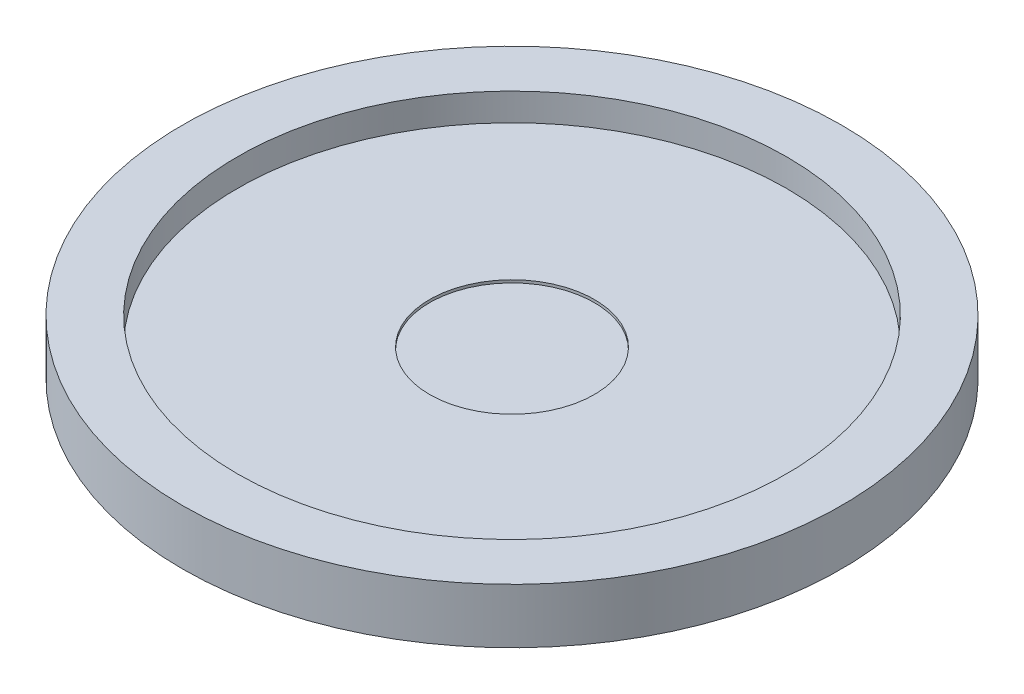
SolidWorks part; units mm, degrees
ref_plane "Front" through (0, 0, 0) normal (0, 0, 1) x (1, 0, 0)
ref_plane "Top" through (0, 0, 0) normal (0, 1, 0) x (1, 0, 0)
ref_plane "Right" through (0, 0, 0) normal (1, 0, 0) x (0, 0, -1)
sketch "Sketch1" plane through (0, 0, 0) normal (0, 1, 0) x (1, 0, 0)
  circle A0 centre (0, 0) radius 12000
  dimension "D1" = 24000
extrude "Boss-Extrude1" add sketch "Sketch1" along normal blind 2000
sketch "Sketch2" plane through (0, 2000, 0) normal (0, 1, 0) x (1, 0, 0)
  circle A0 centre (0, 0) radius 10000
  circle A1 centre (0, 0) radius 12000 construction
  dimension "D1" = 2000
extrude "Cut-Extrude1" cut sketch "Sketch2" against normal blind 1000
sketch "Sketch3" plane through (0, 1000, 0) normal (0, 1, 0) x (1, 0, 0)
  circle A0 centre (0, 0) radius 3000
  dimension "D1" = 6000
extrude "Cut-Extrude2" cut sketch "Sketch3" against normal blind 100
equation "\"Radius\"= 12"
equation "\"diameter\"=24"
equation "\"D1@Sketch1\"=\"diameter\""
equation "\"height\" = 2"
equation "\"D1@Boss-Extrude1\"=\"height\""
equation "\"pit\"=2"
equation "\"D1@Sketch2\"=\"pit\""
equation "\"basehole\"=6"
equation "\"D1@Sketch3\"=\"basehole\""
